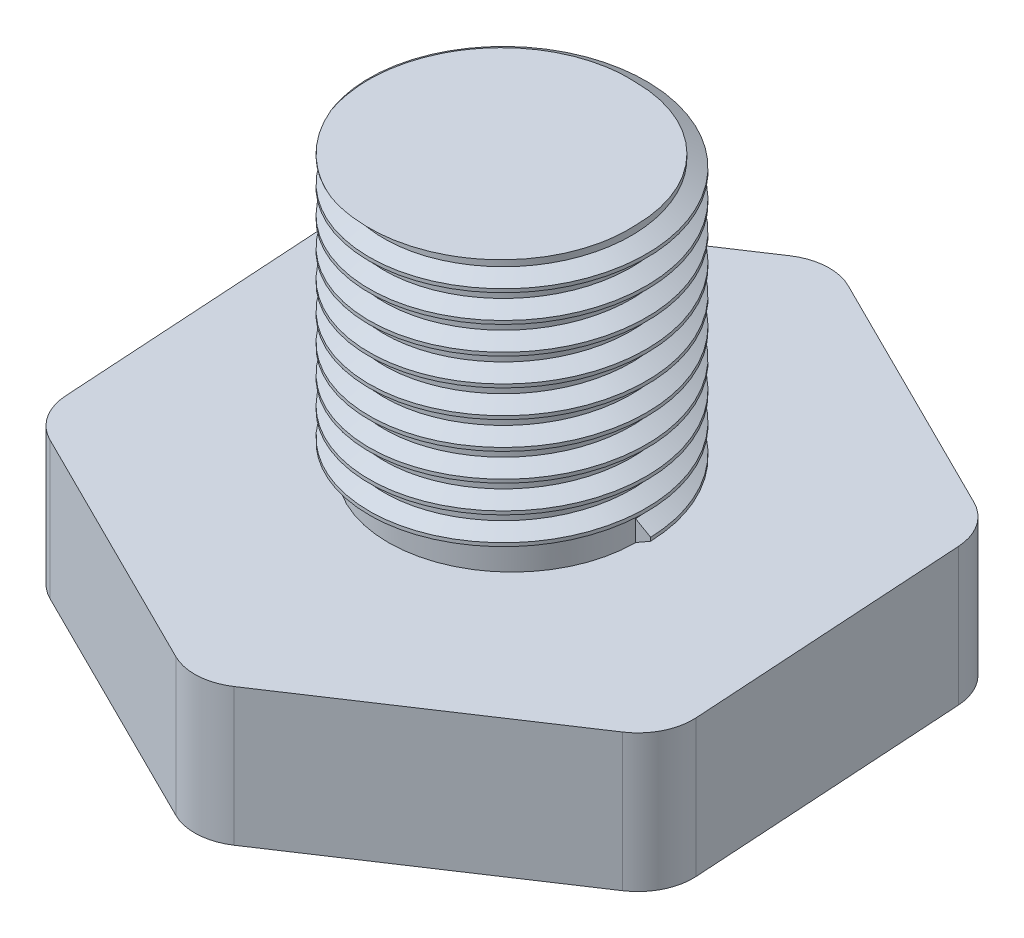
SolidWorks part; units mm, degrees
ref_plane "前视基准面" through (0, 0, 0) normal (0, 0, 1) x (1, 0, 0)
ref_plane "上视基准面" through (0, 0, 0) normal (0, 1, 0) x (1, 0, 0)
ref_plane "右视基准面" through (0, 0, 0) normal (1, 0, 0) x (0, 0, -1)
other "Configuration Table"
sketch "草图1" plane through (0, 0, 0) normal (0, 1, 0) x (1, 0, 0)
  circle A0 centre (0, 0) radius 12.5
  dimension "D1" = 25
extrude "凸台-拉伸1" add sketch "草图1" along normal blind 5
sketch "草图2" plane through (0, 5, 0) normal (0, 1, 0) x (1, 0, 0)
  circle A0 centre (0, 0) radius 4.5
  dimension "D1" = 9
extrude "凸台-拉伸2" add sketch "草图2" along normal blind 10
thread "螺纹线1" pitch 1 method extrude profile "螺纹线轮廓1" start angle 0, offset 0, length 0, pitch 1, diameter 9
ref_plane "基准面1" through (4.5, 5, 0) normal (0, 0, 1) x (1, 0, 0)
sketch "螺纹线轮廓1" plane through (4.5, 5, 0) normal (0, 0, 1) x (1, 0, 0)
  line L0 (0, 0) -> (0, 1) construction
  line L1 (0, 0) -> (0.5413, 0.3125)
  line L2 (0.5413, 0.3125) -> (0.5413, 0.4375)
  line L3 (0.5413, 0.4375) -> (0, 0.75)
  line L4 (0.5413, 0.375) -> (0, 0.375) construction
  line L11 (0, 0) -> (0, 0.75)
  point P2 (0, 0)
  dimension "Pitch" = 1
  dimension "Profile_Angle" = 60
  dimension "Profile_Land" = 0.125
  dimension "Profile_Height" = 0.5413
sketch "草图7" plane through (0, 15, 0) normal (0, 1, 0) x (1, 0, 0)
  circle A0 centre (0, 0) radius 11.1141
extrude "切除-拉伸1" cut sketch "草图7" along normal blind 10
sketch "草图8" plane through (0, 0, 0) normal (0, -1, 0) x (1, 0, 0)
  line L1 (10.4906, -5.753) -> (11.1189, 4.4182)
  line L2 (10.2276, 6.2086) -> (1.7332, 11.8383)
  line L3 (-0.263, 11.9616) -> (-9.3857, 7.4201)
  line L4 (-10.4906, 5.753) -> (-11.1189, -4.4182)
  line L5 (-10.2276, -6.2086) -> (-1.7332, -11.8383)
  line L6 (0.263, -11.9616) -> (9.3857, -7.4201)
  circle A0 centre (0, 0) radius 10.8253 construction
  arc A1 (1.7332, 11.8383) -> (-0.263, 11.9616) centre (0.6283, 10.1712) ccw
  arc A2 (-1.7332, -11.8383) -> (0.263, -11.9616) centre (-0.6283, -10.1712) ccw
  arc A3 (-11.1189, -4.4182) -> (-10.2276, -6.2086) centre (-9.1227, -4.5415) ccw
  arc A4 (-9.3857, 7.4201) -> (-10.4906, 5.753) centre (-8.4944, 5.6297) ccw
  arc A5 (11.1189, 4.4182) -> (10.2276, 6.2086) centre (9.1227, 4.5415) ccw
  arc A6 (10.4906, -5.753) -> (9.3857, -7.4201) centre (8.4944, -5.6297) cw
  dimension "D1" = 2
extrude "切除-拉伸2" cut sketch "草图8" against normal blind 10 flip side to cut
